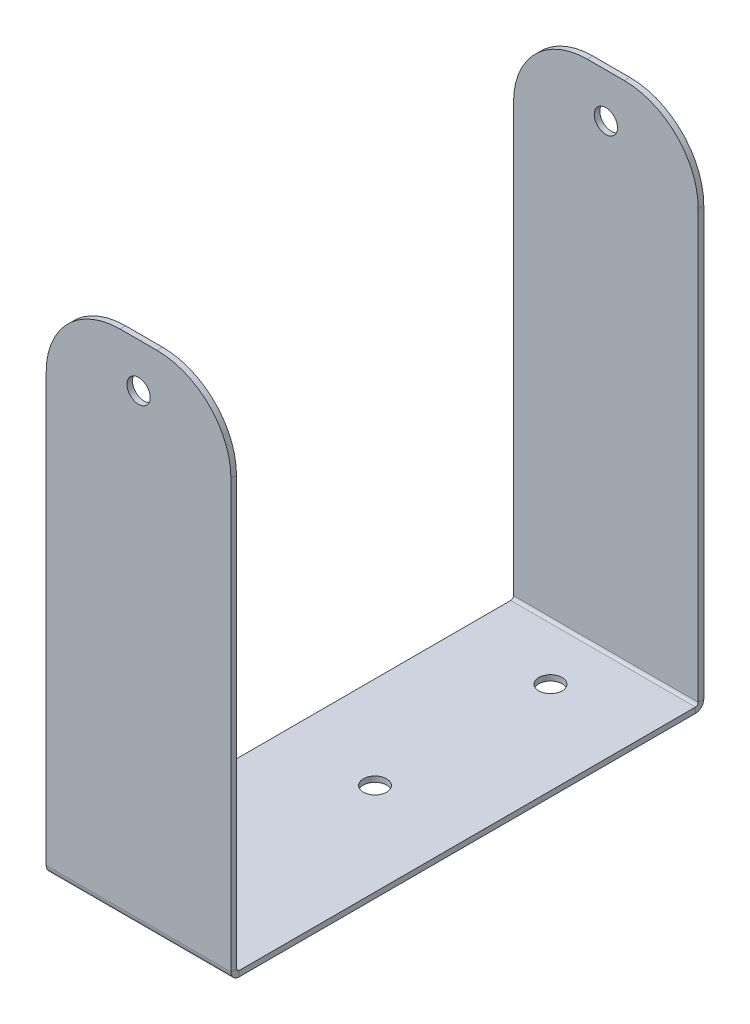
SolidWorks part; units mm, degrees
note: The reader was unsure of these and kept them because the rebuilt part matched: flange length of "Edge-Flange1", "Edge-Flange2".
ref_plane "Front Plane" through (0, 0, 0) normal (0, 0, 1) x (1, 0, 0)
ref_plane "Top Plane" through (0, 0, 0) normal (0, 1, 0) x (1, 0, 0)
ref_plane "Right Plane" through (0, 0, 0) normal (1, 0, 0) x (0, 0, -1)
sketch "Sketch1" plane through (0, 0, 0) normal (0, 1, 0) x (1, 0, 0)
  line L1 (0, 0) -> (50, 0)
  line L2 (0, 0) -> (0, -125)
  line L3 (0, -125) -> (50, -125)
  line L4 (50, 0) -> (50, -125)
  dimension "D1" = 50
  dimension "D2" = 125
base flange "Base-Flange1" sketch "Sketch1" thickness 1.5 reverse thickness direction no parameters "D1"=0.7366
edge flange "Edge-Flange1" sketch "Sketch8" flange angle 90 flange length 138 flange position material outside bend radius 0.75 thickness 1.5 relief rectangular parameters "D6"=10
sketch "Sketch8" plane through (0, 0, 125) normal (0, 0, 1) x (1, 0, 0)
  line L2 (0, 0) -> (0, 136.5)
  line L3 (0, 136.5) -> (50, 136.5)
  line L4 (50, 136.5) -> (50, 0)
  line L7 (0, 0) -> (50, 0) construction
  line L8 (0, 0) -> (50, 0)
bend "EdgeBend1" bend radius 0.75 bend angle 90 parameters "D5"=1
sketch "Sketch9" plane through (0, 0, 126.5) normal (0, 0, 1) x (1, 0, 0)
  line L0 (50, 136.5) -> (0, 136.5) construction
  line L1 (0, 136.5) -> (0, 0.75) construction
  circle A0 centre (25, 124.5) radius 3.15
  dimension "D1" = 6.3
  dimension "D2" = 12
  dimension "D3" = 25
extrude "Cut-Extrude1" cut sketch "Sketch9" against normal blind 176 normal cut yes
edge flange "Edge-Flange2" sketch "Sketch12" flange angle 90 flange length 138 flange position material outside bend radius 0.75 thickness 1.5 relief rectangular parameters "D6"=10
sketch "Sketch12" plane through (0, 0, 0) normal (0, 0, -1) x (-1, 0, 0)
  line L2 (-50, 0) -> (-50, 136.5)
  line L3 (-50, 136.5) -> (0, 136.5)
  line L4 (0, 136.5) -> (0, 0)
  line L7 (-50, 0) -> (0, 0) construction
  line L8 (-50, 0) -> (0, 0)
bend "EdgeBend2" bend radius 0.75 bend angle 90 parameters "D5"=2
sketch "Sketch13" plane through (0, 0, -1.5) normal (0, 0, -1) x (-1, 0, 0)
  line L0 (0, 136.5) -> (-50, 136.5) construction
  line L1 (0, 0.75) -> (0, 136.5) construction
  circle A0 centre (-25, 124.5) radius 3.15
  dimension "D1" = 6.3
  dimension "D2" = 12
  dimension "D3" = 25
extrude "Cut-Extrude2" cut sketch "Sketch13" against normal blind 10 normal cut yes
fillet "Fillet1" radius 20 4 edges at (0, 136.5, -0.75) (50, 136.5, -0.75) (0, 136.5, 125.75) (50, 136.5, 125.75)
sketch "Sketch14" plane through (0, 0, 0) normal (0, 1, 0) x (1, 0, 0)
  line L0 (25, -0.75) -> (25, -124.25) construction
  line L1 (0, -0.75) -> (50, -0.75) construction
  line L2 (50, -124.25) -> (0, -124.25) construction
  line L3 (50, 0) -> (0, 0) construction
  line L4 (0, -125) -> (50, -125) construction
  line L5 (20, -125) -> (0, -125) construction
  circle A0 centre (25, -15) radius 3.15
  circle A1 centre (25, -62.5) radius 3.15
  circle A2 centre (25, -110) radius 3.15
  dimension "D1" = 6.3
  dimension "D2" = 6.3
  dimension "D3" = 6.3
  dimension "D4" = 15
  dimension "D5" = 15
extrude "Cut-Extrude3" cut sketch "Sketch14" against normal blind 10 normal cut yes
sketch "Bend-Lines1" [suppressed] plane through (0, 0, 0) normal (0, 1, 0) x (1, 0, 0)
sketch "Bounding-Box1" [suppressed] plane through (0, 0, 0) normal (0, 1, 0) x (1, 0, 0)
sheet metal parameters "Sheet-Metal1" thickness 1.5 parameters "D1"=0.7366
flat pattern "Flat-Pattern1" [suppressed]
sketch "Bend-Lines2" plane through (0, 0, 0) normal (0, 1, 0) x (1, 0, 0)
sketch3d "Bounding-Box2" [suppressed]
  line L0 (0, 0, 0) -> (0, -122, 0) construction
  line L1 (-50, 0, 0) -> (-50, -122, 0) construction
  line L2 (0, 0, 0) -> (-50, 0, 0) construction
  line L3 (0, -122, 0) -> (-50, -122, 0) construction
sheet metal parameters "Sheet-Metal2" thickness 1.5 parameters "D1"=0.7366
flat pattern "Flat-Pattern1"
sketch "Bend-Lines2" plane through (0, 0, 0) normal (0, 1, 0) x (1, 0, 0)
  line L0 (0, -122.2514) -> (50, -122.2514) construction
  line L1 (0, -122.2514) -> (50, -122.2514) construction
sketch3d "Bounding-Box2" [suppressed]
  line L0 (0, 0, 0) -> (0, -259.0028, 0) construction
  line L1 (50, 0, 0) -> (50, -259.0028, 0) construction
  line L2 (0, 0, 0) -> (50, 0, 0) construction
  line L3 (0, -259.0028, 0) -> (50, -259.0028, 0) construction
bend of the flat pattern "Flatten-<EdgeBend1>1"
sheet metal parameters "Sheet-Metal3" thickness 1.5 parameters "D1"=0.7366
flat pattern "Flat-Pattern1"
sketch "Bend-Lines2" plane through (0, 0, 0) normal (0, 1, 0) x (1, 0, 0)
  line L0 (0, -122.2514) -> (50, -122.2514) construction
  line L1 (0, -122.2514) -> (50, -122.2514) construction
sketch3d "Bounding-Box2" [suppressed]
  line L0 (0, 0, 0) -> (0, -259.0028, 0) construction
  line L1 (50, 0, 0) -> (50, -259.0028, 0) construction
  line L2 (0, 0, 0) -> (50, 0, 0) construction
  line L3 (0, -259.0028, 0) -> (50, -259.0028, 0) construction
bend of the flat pattern "Flatten-<EdgeBend1>1"
sheet metal parameters "Sheet-Metal4" thickness 1.5 parameters "D1"=0.7366
flat pattern "Flat-Pattern1"
sketch "Bend-Lines2" plane through (0, 0, 0) normal (0, 1, 0) x (1, 0, 0)
  line L0 (0, -122.2514) -> (50, -122.2514) construction
  line L1 (0, -122.2514) -> (50, -122.2514) construction
  line L2 (50, 0.2514) -> (0, 0.2514) construction
  line L3 (50, 0.2514) -> (0, 0.2514) construction
sketch3d "Bounding-Box2" [suppressed]
  line L0 (0, 137.0028, 0) -> (0, -259.0028, 0) construction
  line L1 (50, 137.0028, 0) -> (50, -259.0028, 0) construction
  line L2 (0, 137.0028, 0) -> (50, 137.0028, 0) construction
  line L3 (0, -259.0028, 0) -> (50, -259.0028, 0) construction
bend of the flat pattern "Flatten-<EdgeBend1>1"
bend of the flat pattern "Flatten-<EdgeBend2>1"
sheet metal parameters "Sheet-Metal5" thickness 1.5 parameters "D1"=0.7366
flat pattern "Flat-Pattern1"
sketch "Bend-Lines2" plane through (0, 0, 0) normal (0, 1, 0) x (1, 0, 0)
  line L0 (0, -122.2514) -> (50, -122.2514) construction
  line L1 (0, -122.2514) -> (50, -122.2514) construction
  line L2 (50, 0.2514) -> (0, 0.2514) construction
  line L3 (50, 0.2514) -> (0, 0.2514) construction
sketch3d "Bounding-Box2" [suppressed]
  line L0 (0, 137.0028, 0) -> (0, -259.0028, 0) construction
  line L1 (50, 137.0028, 0) -> (50, -259.0028, 0) construction
  line L2 (0, 137.0028, 0) -> (50, 137.0028, 0) construction
  line L3 (0, -259.0028, 0) -> (50, -259.0028, 0) construction
bend of the flat pattern "Flatten-<EdgeBend1>1"
bend of the flat pattern "Flatten-<EdgeBend2>1"
sheet metal parameters "Sheet-Metal6" thickness 1.5 parameters "D1"=0.7366
flat pattern "Flat-Pattern1"
sketch "Bend-Lines2" plane through (0, 0, 0) normal (0, 1, 0) x (1, 0, 0)
  line L0 (0, -125.2514) -> (50, -125.2514) construction
  line L1 (0, -125.2514) -> (50, -125.2514) construction
  line L2 (50, 0.2514) -> (0, 0.2514) construction
  line L3 (50, 0.2514) -> (0, 0.2514) construction
sketch3d "Bounding-Box2" [suppressed]
  line L0 (0, 137.0028, 0) -> (0, -262.0028, 0) construction
  line L1 (50, 137.0028, 0) -> (50, -262.0028, 0) construction
  line L2 (0, 137.0028, 0) -> (50, 137.0028, 0) construction
  line L3 (0, -262.0028, 0) -> (50, -262.0028, 0) construction
bend of the flat pattern "Flatten-<EdgeBend1>1"
bend of the flat pattern "Flatten-<EdgeBend2>1"
